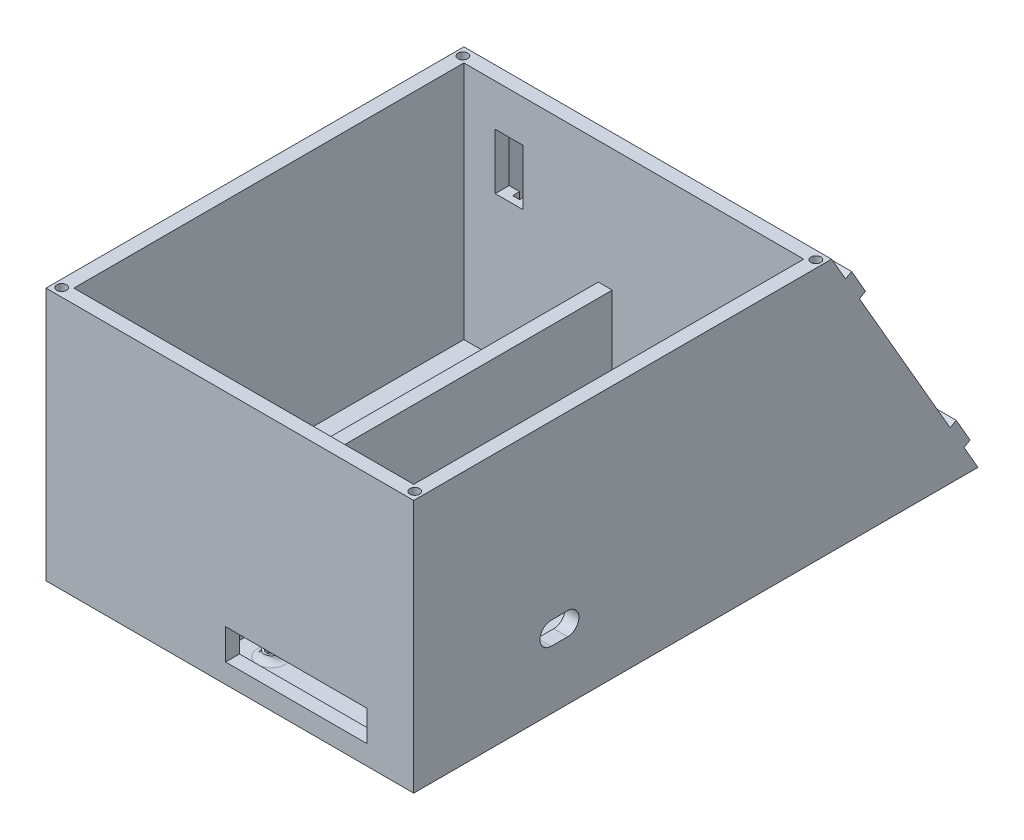
SolidWorks part; units mm, degrees
ref_plane "Front Plane" through (0, 0, 0) normal (0, 0, 1) x (1, 0, 0)
ref_plane "Top Plane" through (0, 0, 0) normal (0, 1, 0) x (1, 0, 0)
ref_plane "Right Plane" through (0, 0, 0) normal (1, 0, 0) x (0, 0, -1)
sketch "Sketch1" plane through (0, 0, 0) normal (0, 1, 0) x (1, 0, 0)
  line L1 (-66, 75) -> (66, 75)
  line L2 (-66, 75) -> (-66, -75)
  line L3 (-66, -75) -> (66, -75)
  line L4 (66, 75) -> (66, -75)
  line L5 (-66, 75) -> (66, -75) construction
  line L6 (-66, -75) -> (66, 75) construction
  point P4 (0, 0)
  dimension "D1" = 150
  dimension "D2" = 132
extrude "Boss-Extrude1" add sketch "Sketch1" along normal blind 91
sketch "Sketch2" plane through (0, 91, 0) normal (0, 1, 0) x (1, 0, 0)
  line L1 (61, -70) -> (-61, -70)
  line L2 (61, -70) -> (61, 70)
  line L3 (61, 70) -> (-61, 70)
  line L4 (-61, -70) -> (-61, 70)
  line L5 (61, -70) -> (-61, 70) construction
  line L6 (61, 70) -> (-61, -70) construction
  line L7 (-66, -75) -> (66, -75) construction
  line L8 (66, 75) -> (-66, 75) construction
  point P4 (0, 0)
  dimension "D1" = 122
  dimension "D2" = 5
  dimension "D3" = 5
extrude "Cut-Extrude1" cut sketch "Sketch2" against normal blind 86
sketch "Sketch4" plane through (0, 5, 0) normal (0, 1, 0) x (1, 0, 0)
  line L0 (-61, -70) -> (61, -70) construction
  line L1 (57.5, -67.5) -> (-6.5, -67.5) construction
  line L2 (57.5, -67.5) -> (57.5, 12.5) construction
  line L3 (57.5, 12.5) -> (-6.5, 12.5) construction
  line L4 (-6.5, -67.5) -> (-6.5, 12.5) construction
  line L5 (57.5, -67.5) -> (-6.5, 12.5) construction
  line L6 (57.5, 12.5) -> (-6.5, -67.5) construction
  line L7 (61, -70) -> (61, 70) construction
  line L8 (61, 70) -> (-61, 70) construction
  line L9 (-7.75, -70) -> (-12.75, -70)
  line L10 (-7.75, -70) -> (-7.75, 70)
  line L11 (-7.75, 70) -> (-12.75, 70)
  line L12 (-12.75, -70) -> (-12.75, 70)
  line L13 (-7.75, -70) -> (-12.75, 70) construction
  line L14 (-7.75, 70) -> (-12.75, -70) construction
  line L15 (-61, 70) -> (-61, -70) construction
  line L16 (-17, -67.5) -> (-57.5, -67.5) construction
  line L17 (-17, -67.5) -> (-17, 12.5) construction
  line L18 (-17, 12.5) -> (-57.5, 12.5) construction
  line L19 (-57.5, -67.5) -> (-57.5, 12.5) construction
  line L20 (-17, -67.5) -> (-57.5, 12.5) construction
  line L21 (-17, 12.5) -> (-57.5, -67.5) construction
  line L22 (-61, -70) -> (61, -70) construction
  point P4 (25.5, -27.5)
  point P13 (-10.25, 0)
  point P20 (-37.25, -27.5)
  dimension "D1" = 64
  dimension "D2" = 80
  dimension "D3" = 2.5
  dimension "D4" = 3.5
  dimension "D5" = 4.25
  dimension "D6" = 5
  dimension "D7" = 40.5
  dimension "D8" = 80
  dimension "D9" = 3.5
  dimension "D10" = 2.5
  dimension "D11" = 1.25
extrude "Boss-Extrude2" add sketch "Sketch4" along normal blind 42
sketch "Sketch7" plane through (-7.75, 0, 0) normal (1, 0, 0) x (0, 0, -1)
  line L0 (-70, 47) -> (-70, 5) construction
  line L6 (-53.3633, 25) -> (-48.3633, 25)
  line L9 (-53.3633, 25) -> (-53.3633, 15)
  line L10 (-53.3633, 15) -> (-48.3633, 15)
  line L11 (-48.3633, 25) -> (-48.3633, 15)
  line L12 (-53.3633, 25) -> (-48.3633, 15) construction
  line L13 (-53.3633, 15) -> (-48.3633, 25) construction
  line L14 (-70, 5) -> (70, 5) construction
  dimension "D1" = 5
  dimension "D2" = 10
  dimension "D3" = 10
  dimension "D4" = 16.6367
extrude "Cut-Extrude3" cut sketch "Sketch7" against normal blind 10
sketch "Sketch8" plane through (0, 5, 0) normal (0, 1, 0) x (1, 0, 0)
  line L3 (61, 0) -> (-7.75, 0) construction
  line L4 (61, -70) -> (61, 70) construction
  line L5 (-7.75, -70) -> (-7.75, 70) construction
  line L6 (-36.875, -70) -> (-36.875, 70) construction
  line L7 (-61, -70) -> (-12.75, -70) construction
  line L8 (-12.75, 70) -> (-61, 70) construction
  line L9 (-12.75, 0) -> (-61, 0) construction
  line L10 (-12.75, 70) -> (-12.75, -70) construction
  line L11 (-61, 70) -> (-61, -70) construction
  circle A0 centre (26.625, 0) radius 1.75
  circle A1 centre (-36.875, 0) radius 1.7
  point P30 (-36.875, 0)
  dimension "D1" = 3.5
  dimension "D2" = 3.4
extrude "Cut-Extrude4" cut sketch "Sketch8" against normal blind 10
sketch "Sketch9" plane through (0, 5, 0) normal (0, 1, 0) x (1, 0, 0)
  circle A0 centre (26.625, 0) radius 4
  circle A1 centre (-36.875, 0) radius 4
  dimension "D1" = 8
  dimension "D2" = 8
extrude "Cut-Extrude6" cut sketch "Sketch9" against normal blind 2
sketch "Sketch15" plane through (0, 91, 0) normal (0, 1, 0) x (1, 0, 0)
  line L0 (66, -75) -> (-66, 75) construction
  line L1 (66, -75) -> (-66, -75) construction
  line L2 (66, -75) -> (66, 75) construction
  line L3 (66, 75) -> (-66, 75) construction
  line L4 (-66, -75) -> (-66, 75) construction
  line L5 (0, 75) -> (0, -75) construction
  line L6 (66, 0) -> (-66, 0) construction
  line L7 (-66, -75) -> (66, 75) construction
  circle A2 centre (63.3575, -71.9971) radius 1.75
  circle A3 centre (-63.3575, -71.9971) radius 1.75
  circle A4 centre (-63.3575, 71.9971) radius 1.75
  circle A5 centre (63.3575, 71.9971) radius 1.75
  point P283 (0, 0)
  dimension "D1" = 3.5
  dimension "D2" = 4
extrude "Cut-Extrude10" cut sketch "Sketch15" against normal blind 10
sketch "Sketch20" plane through (0, 5, 0) normal (0, 1, 0) x (1, 0, 0)
  line L0 (2.975, -63.125) -> (2.975, 13.125) construction
  line L1 (2.975, 13.125) -> (50.275, 13.125) construction
  line L2 (50.275, 13.125) -> (50.275, -63.125) construction
  line L3 (50.275, -63.125) -> (2.975, -63.125) construction
  line L4 (61, -70) -> (61, 70) construction
  line L5 (-7.75, -70) -> (61, -70) construction
  circle A0 centre (2.975, -63.125) radius 1.75
  circle A1 centre (2.975, 13.125) radius 1.75
  circle A2 centre (50.275, 13.125) radius 1.75
  circle A3 centre (50.275, -63.125) radius 1.75
  circle A4 centre (2.975, -63.125) radius 2.5
  circle A5 centre (2.975, 13.125) radius 2.5
  circle A6 centre (50.275, 13.125) radius 2.5
  circle A7 centre (50.275, -63.125) radius 2.5
  dimension "D1" = 3.5
  dimension "D2" = 3.5
  dimension "D3" = 3.5
  dimension "D4" = 3.5
  dimension "D7" = 5
  dimension "D8" = 5
  dimension "D9" = 5
  dimension "D10" = 5
  dimension "D12" = 6.875
  dimension "D5" = 76.25
  dimension "D6" = 47.3
  dimension "D11" = 10.725
extrude "Boss-Extrude3" add sketch "Sketch20" along normal blind 2
fillet "Fillet1" radius 2.5 4 edges at (50.275, 5, -10.625) (50.275, 5, 65.625) (2.975, 5, -10.625) (2.975, 5, 65.625) first distance on face at (50.275, 5, 65.625)
sketch "Sketch21" plane through (0, 0, 70) normal (0, 0, -1) x (-1, 0, 0)
  line L0 (-61, 5) -> (-61, 91) construction
  line L1 (-58.77, 29.2) -> (5.53, 29.2) construction
  line L2 (-58.77, 29.2) -> (-58.77, 7) construction
  line L3 (-58.77, 7) -> (5.53, 7) construction
  line L4 (5.53, 29.2) -> (5.53, 7) construction
  line L5 (-26.62, 7) -> (-26.62, 29.2) construction
  line L6 (-58.77, 18.1) -> (5.53, 18.1) construction
  line L7 (7.75, 47) -> (7.75, 5) construction
  line L8 (7.75, 5) -> (-61, 5) construction
  line L10 (-49.27, 18) -> (1.53, 18)
  line L11 (-49.27, 18) -> (-49.27, 7)
  line L12 (-49.27, 7) -> (1.53, 7)
  line L13 (1.53, 18) -> (1.53, 7)
  line L14 (-23.87, 7) -> (-23.87, 18) construction
  line L15 (-49.27, 12.5) -> (1.53, 12.5) construction
  point P214 (-23.87, 12.5)
  point P260 (-26.62, 18.1)
  dimension "D1" = 22.2
  dimension "D2" = 2.23
  dimension "D3" = 2.22
  dimension "D4" = 2
  dimension "D5" = 9.5
  dimension "D6" = 4
  dimension "D7" = 11
extrude "Cut-Extrude15" cut sketch "Sketch21" against normal blind 10
sketch "Sketch22" plane through (61, 0, 0) normal (-1, 0, 0) x (0, 0, 1)
  line L0 (-70, 5) -> (-70, 91) construction
  line L1 (-67.77, 29.2) -> (67.78, 29.2) construction
  line L2 (-67.77, 29.2) -> (-67.77, 7) construction
  line L3 (-67.77, 7) -> (67.78, 7) construction
  line L4 (67.78, 29.2) -> (67.78, 7) construction
  line L5 (0.005, 7) -> (0.005, 29.2) construction
  line L6 (-67.77, 18.1) -> (67.78, 18.1) construction
  line L7 (70, 5) -> (70, 91) construction
  line L8 (70, 5) -> (-70, 5) construction
  line L9 (19.76, 25.05) -> (25.66, 25.05) construction
  line L10 (19.76, 29.1) -> (25.66, 29.1)
  line L11 (19.76, 21) -> (25.66, 21)
  arc A0 (19.76, 29.1) -> (19.76, 21) centre (19.76, 25.05) ccw
  arc A1 (25.66, 21) -> (25.66, 29.1) centre (25.66, 25.05) ccw
  point P12 (22.71, 25.05)
  point P17 (15.71, 25.05)
  point P18 (29.71, 25.05)
  point P188 (0.005, 18.1)
  dimension "D6" = 42.12
  dimension "D1" = 2.23
  dimension "D2" = 2.22
  dimension "D3" = 2
  dimension "D4" = 22.2
  dimension "D5" = 8.1
  dimension "D7" = 14
  dimension "D8" = 14
extrude "Cut-Extrude16" cut sketch "Sketch22" against normal blind 10
sketch "Sketch26" plane through (0, 0, -75) normal (0, 0, -1) x (-1, 0, 0)
  line L0 (43.5, 22.5) -> (43.5, 56)
  line L5 (22.4, 35) -> (30.25, 35)
  line L6 (22.4, 76) -> (30.25, 76)
  line L7 (43.5, 56) -> (46, 56)
  line L9 (43.5, 20) -> (46, 20)
  line L10 (46, 56) -> (46, 20)
  line L11 (44.75, 20) -> (44.75, 56) construction
  line L12 (43.5, 38) -> (46, 38) construction
  line L14 (43.5, 20) -> (19.9, 20)
  line L16 (43.5, 22.5) -> (22.4, 22.5)
  line L17 (19.9, 20) -> (19.9, 22.5)
  line L18 (31.7, 22.5) -> (31.7, 20) construction
  line L19 (43.5, 21.25) -> (19.9, 21.25) construction
  line L21 (19.9, 22.5) -> (19.9, 35)
  line L23 (22.4, 22.5) -> (22.4, 35)
  line L24 (18.9172, 35) -> (18.9172, 22.5) construction
  line L25 (19.9, 28.75) -> (22.4, 28.75) construction
  line L26 (12.05, 76) -> (19.9, 76)
  line L27 (12.05, 76) -> (12.05, 35)
  line L28 (12.05, 35) -> (19.9, 35)
  line L29 (30.25, 76) -> (30.25, 35)
  line L30 (18.9172, 35) -> (18.9172, 76) construction
  line L31 (12.05, 55.5) -> (30.25, 55.5) construction
  line L33 (22.4, 76) -> (22.4, 83)
  line L35 (19.9, 76) -> (19.9, 83)
  line L36 (18.9172, 83) -> (18.9172, 76) construction
  line L37 (-21.95, 75.5) -> (-15.95, 75.5)
  line L38 (19.9, 83) -> (-21.95, 83)
  line L39 (22.4, 83) -> (22.4, 85.5)
  line L40 (22.4, 85.5) -> (-24.45, 85.5)
  line L41 (-24.45, 83) -> (-24.45, 85.5)
  line L42 (-1.025, 85.5) -> (-1.025, 83) construction
  line L43 (22.4, 84.25) -> (-24.45, 84.25) construction
  line L45 (-24.45, 83) -> (-24.45, 75.5)
  line L47 (-21.95, 83) -> (-21.95, 75.5)
  line L48 (-23.2, 75.5) -> (-23.2, 83) construction
  line L49 (-21.95, 13.5) -> (-15.95, 13.5)
  line L50 (-30.45, 75.5) -> (-24.45, 75.5)
  line L51 (-30.45, 75.5) -> (-30.45, 13.5)
  line L52 (-30.45, 13.5) -> (-24.45, 13.5)
  line L53 (-15.95, 75.5) -> (-15.95, 13.5)
  line L54 (-23.2, 13.5) -> (-23.2, 75.5) construction
  line L55 (-30.45, 44.5) -> (-15.95, 44.5) construction
  line L57 (-21.95, 13.5) -> (-21.95, 6)
  line L58 (-21.95, 6) -> (-24.45, 6)
  line L59 (-24.45, 13.5) -> (-24.45, 8.5)
  line L60 (-23.2, 9.75) -> (-23.2, 13.5) construction
  line L61 (66, 91) -> (66, 0) construction
  line L62 (-24.45, 6) -> (-53.45, 6)
  line L64 (-24.45, 8.5) -> (-53.45, 8.5)
  line L65 (-53.45, 6) -> (-53.45, 8.5)
  line L66 (-38.95, 8.5) -> (-38.95, 6) construction
  line L67 (-20.65, 7.25) -> (-53.45, 7.25) construction
  point P90 (-23.2, 79.25)
  point P123 (-23.2, 9.75)
  point P140 (18.9172, 79.5)
  point P149 (-1.025, 84.25)
  point P156 (18.9172, 55.5)
  point P161 (31.7, 21.25)
  point P182 (-23.2, 44.5)
  point P185 (-38.95, 7.25)
  point P229 (18.9172, 28.75)
  point P281 (44.75, 38)
  dimension "D3" = 2.5
  dimension "D4" = 36
  dimension "D5" = 20
  dimension "D7" = 23.6
  dimension "D8" = 12.5
  dimension "D9" = 2.5
  dimension "D10" = 2.5
  dimension "D11" = 41
  dimension "D12" = 18.2
  dimension "D13" = 7.85
  dimension "D14" = 2.5
  dimension "D15" = 7
  dimension "D16" = 46.85
  dimension "D17" = 2.5
  dimension "D18" = 7.5
  dimension "D19" = 2.5
  dimension "D20" = 14.5
  dimension "D21" = 62
  dimension "D22" = 2.5
  dimension "D23" = 7.5
  dimension "D24" = 2.5
  dimension "D25" = 29
extrude "Cut-Extrude17" cut sketch "Sketch26" against normal blind 2.5
sketch "Sketch28" plane through (0, 0, -75) normal (0, 0, -1) x (-1, 0, 0)
  line L0 (-24.45, 8.5) -> (-53.45, 8.5) construction
  line L1 (-53.45, 6) -> (-58.85, 6)
  line L2 (-53.45, 6) -> (-53.45, 8.5)
  line L3 (-53.45, 8.5) -> (-58.85, 8.5)
  line L4 (-58.85, 6) -> (-58.85, 8.5)
  line L5 (-56.15, 8.5) -> (-56.15, 6) construction
  line L6 (-53.45, 7.25) -> (-58.85, 7.25) construction
  point P168 (-56.15, 7.25)
  dimension "D1" = 5.4
extrude "Cut-Extrude19" cut sketch "Sketch28" against normal blind 5.5
sketch "Sketch29" plane through (0, 0, -75) normal (0, 0, -1) x (-1, 0, 0)
  line L0 (46, 56) -> (43.5, 56) construction
  line L1 (39.75, 76) -> (49.75, 76)
  line L2 (39.75, 76) -> (39.75, 56)
  line L3 (39.75, 56) -> (49.75, 56)
  line L4 (49.75, 76) -> (49.75, 56)
  line L5 (44.75, 56) -> (44.75, 76) construction
  line L6 (39.75, 66) -> (49.75, 66) construction
  line L7 (46, 20) -> (46, 56) construction
  point P164 (44.75, 66)
  dimension "D1" = 10
  dimension "D2" = 20
  dimension "D3" = 3.75
extrude "Cut-Extrude20" cut sketch "Sketch29" against normal blind 20.5
sketch "Sketch30" plane through (66, 0, 0) normal (1, 0, 0) x (0, 0, -1)
  line L0 (75, 91) -> (127.5389, 0)
  line L1 (127.5389, 0) -> (75, 0)
  line L2 (75, 0) -> (75, 91)
  dimension "D1" = 30
extrude "Boss-Extrude6" add sketch "Sketch30" against normal blind 5 contours L2 L0 L1
sketch "Sketch31" plane through (-66, 0, 0) normal (-1, 0, 0) x (0, 0, 1)
  line L0 (-75, 91) -> (-127.5389, 0)
  line L1 (-127.5389, 0) -> (-75, 0)
  line L2 (-75, 0) -> (-75, 91)
  dimension "D1" = 30
extrude "Boss-Extrude7" add sketch "Sketch31" against normal blind 5
sketch "Sketch32" plane through (0, 55.226, -95.6542) normal (0, 0.5, -0.866) x (-1, 0, 0)
  line L0 (-66, 41.3083) -> (-66, -63.7694) construction
  line L1 (-66, 31.3083) -> (-53, 31.3083)
  line L2 (-66, 31.3083) -> (-66, 21.3083)
  line L3 (-66, 21.3083) -> (-53, 21.3083)
  line L4 (-53, 31.3083) -> (-53, 21.3083)
  line L5 (-59.5, 21.3083) -> (-59.5, 31.3083) construction
  line L6 (-66, 26.3083) -> (-53, 26.3083) construction
  line L7 (66, 41.3083) -> (66, -63.7694) construction
  line L8 (-66, -43.7694) -> (-53, -43.7694)
  line L9 (-66, -43.7694) -> (-66, -53.7694)
  line L10 (-66, -53.7694) -> (-53, -53.7694)
  line L11 (-53, -43.7694) -> (-53, -53.7694)
  line L12 (-59.5, -53.7694) -> (-59.5, -43.7694) construction
  line L13 (-66, -48.7694) -> (-53, -48.7694) construction
  line L14 (66, 31.3083) -> (53, 31.3083)
  line L15 (66, 31.3083) -> (66, 21.3083)
  line L16 (66, 21.3083) -> (53, 21.3083)
  line L17 (53, 31.3083) -> (53, 21.3083)
  line L18 (59.5, 21.3083) -> (59.5, 31.3083) construction
  line L19 (66, 26.3083) -> (53, 26.3083) construction
  line L20 (-61, -63.7694) -> (-66, -63.7694) construction
  line L21 (66, -43.7694) -> (53, -43.7694)
  line L22 (66, -43.7694) -> (66, -53.7694)
  line L23 (66, -53.7694) -> (53, -53.7694)
  line L24 (53, -43.7694) -> (53, -53.7694)
  line L25 (59.5, -53.7694) -> (59.5, -43.7694) construction
  line L26 (66, -48.7694) -> (53, -48.7694) construction
  line L27 (-66, 41.3083) -> (-61, 41.3083) construction
  point P56 (59.5, -48.7694)
  point P116 (-59.5, 26.3083)
  point P119 (-59.5, -48.7694)
  point P144 (59.5, 26.3083)
  dimension "D1" = 13
  dimension "D2" = 10
  dimension "D3" = 13
  dimension "D4" = 10
  dimension "D5" = 13
  dimension "D6" = 10
  dimension "D7" = 13
  dimension "D8" = 10
  dimension "D9" = 10
  dimension "D10" = 10
extrude "Boss-Extrude8" add sketch "Sketch32" along normal blind 2.5
sketch "Sketch33" plane through (0, 56.476, -97.8192) normal (0, 0.5, -0.866) x (-1, 0, 0)
  line L0 (-59.5, 31.3083) -> (-59.5, 21.3083) construction
  line L1 (-53, 31.3083) -> (-66, 31.3083) construction
  line L2 (-66, 21.3083) -> (-53, 21.3083) construction
  line L3 (-59.5, -43.7694) -> (-59.5, -53.7694) construction
  line L4 (-53, -43.7694) -> (-66, -43.7694) construction
  line L5 (-66, -53.7694) -> (-53, -53.7694) construction
  line L6 (59.5, -53.7694) -> (59.5, -43.7694) construction
  line L9 (53, -53.7694) -> (66, -53.7694) construction
  line L10 (66, -43.7694) -> (53, -43.7694) construction
  line L11 (59.5, 31.3083) -> (59.5, 21.3083) construction
  line L12 (66, 31.3083) -> (53, 31.3083) construction
  line L13 (53, 21.3083) -> (66, 21.3083) construction
  circle A0 centre (-59.5, 26.3083) radius 1.75
  circle A1 centre (-59.5, -48.7694) radius 1.75
  circle A2 centre (59.5, 26.3083) radius 1.75
  circle A3 centre (59.5, -48.7694) radius 1.75
  dimension "D1" = 3.5
  dimension "D2" = 3.5
  dimension "D3" = 3.5
  dimension "D4" = 3.5
extrude "Cut-Extrude21" cut sketch "Sketch33" against normal blind 4
